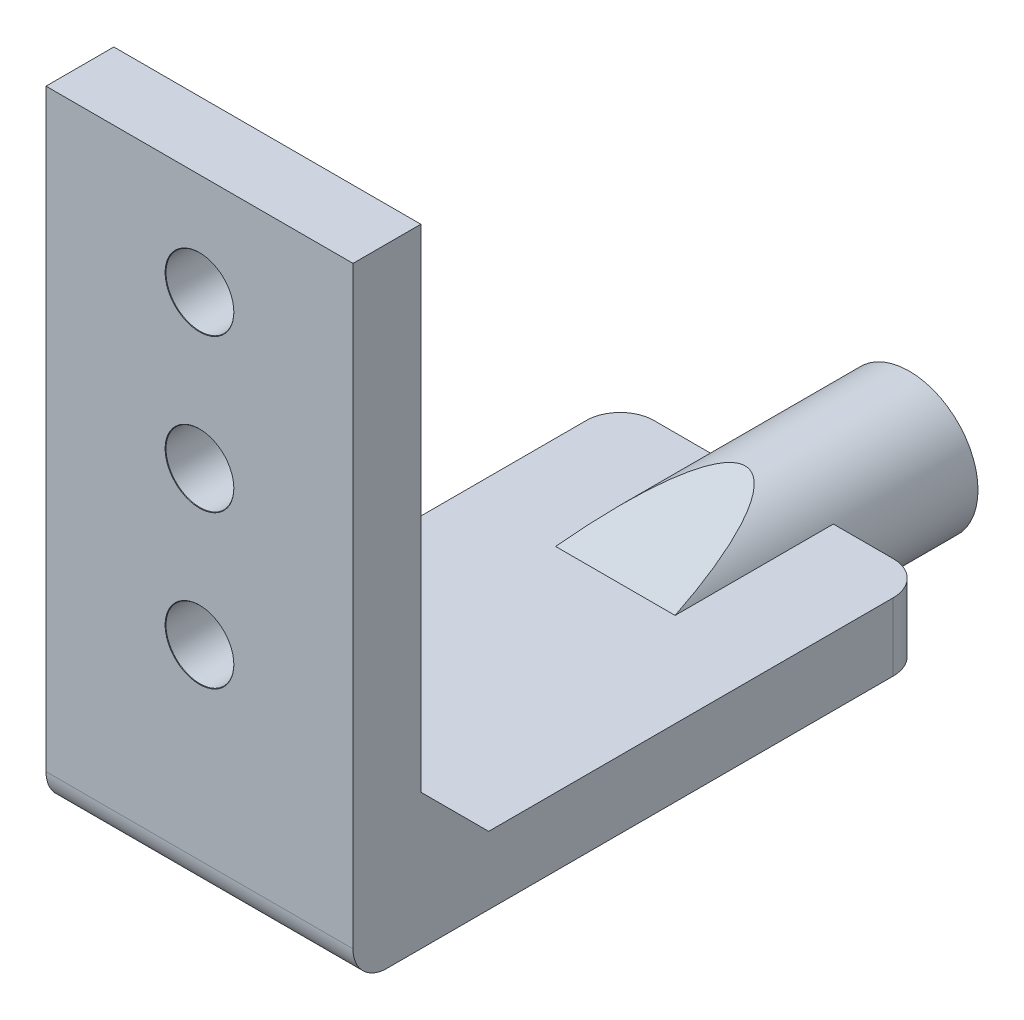
SolidWorks part; units mm, degrees
material "ABS"
ref_plane "Front Plane" through (0, 0, 0) normal (0, 0, 1) x (1, 0, 0)
ref_plane "Top Plane" through (0, 0, 0) normal (0, 1, 0) x (1, 0, 0)
ref_plane "Right Plane" through (0, 0, 0) normal (1, 0, 0) x (0, 0, -1)
sketch "Sketch1" plane through (0, 0, 0) normal (0, 0, 1) x (1, 0, 0)
  circle A0 centre (0, 0) radius 4.05
  dimension "D1" = 8.1
extrude "Boss-Extrude1" add sketch "Sketch1" along normal blind 8
sketch "Sketch2" plane through (0, 0, 8) normal (0, 0, 1) x (1, 0, 0)
  line L1 (-9.05, -2) -> (9.05, -2)
  line L2 (-9.05, -2) -> (-9.05, 2)
  line L3 (-9.05, 2) -> (9.05, 2)
  line L4 (9.05, -2) -> (9.05, 2)
  line L5 (-9.05, -2) -> (9.05, 2) construction
  line L6 (-9.05, 2) -> (9.05, -2) construction
  point P0 (0, 0)
  dimension "D1" = 4
  dimension "D2" = 18.1
extrude "Boss-Extrude2" add sketch "Sketch2" along normal blind 33.85
chamfer "Chamfer1" distance 2.5 angle 75 1 edges at (0, 2, 8) first distance on face at (0, 3.025, 8)
chamfer "Chamfer2" distance 2.5 angle 75 1 edges at (0, -2, 8) first distance on face at (0, -3.025, 8)
fillet "Fillet1" radius 2 2 edges at (-9.05, 0, 8) (9.05, 0, 8)
sketch "Sketch3" plane through (0, 2, 0) normal (0, 1, 0) x (1, 0, 0)
  line L0 (9.05, -41.85) -> (9.05, -10) construction
  line L1 (-9.05, -41.85) -> (9.05, -41.85)
  line L2 (-9.05, -41.85) -> (-9.05, -37.85)
  line L3 (-9.05, -37.85) -> (9.05, -37.85)
  line L4 (9.05, -41.85) -> (9.05, -37.85)
  dimension "D1" = 4
extrude "Boss-Extrude3" add sketch "Sketch3" along normal blind 33
chamfer "Chamfer3" distance 4 angle 45 1 edges at (0, 2, 37.85)
hole_wizard "Ø4.0mm Dowel Hole1" positions "Sketch4" profile "Sketch5" hole size "Ø4.0" standard "ANSI Metric" end condition through all
sketch "Sketch4" plane through (0, 0, 41.85) normal (0, 0, 1) x (1, 0, 0)
  line L0 (-9.05, 35) -> (9.05, 35) construction
  point P0 (0, 29)
  point P2 (0, 20)
  point P4 (0, 11)
  point P6 (0, 0)
  point P7 (0, 0)
  point P8 (0, 0)
  point P9 (0, 0)
  dimension "D1" = 6
  dimension "D2" = 9
  dimension "D3" = 9
sketch "Sketch5" plane through (0, 29, 41.85) normal (1, 0, 0) x (0, -1, 0)
  line L0 (0, 0) -> (0, 41.85)
  line L1 (0, 41.85) -> (2, 41.85)
  line L2 (2, 41.85) -> (2, 0.025)
  line L3 (2, 0.025) -> (2.025, 0)
  line L5 (2.025, 0) -> (0, 0)
  line L6 (-2, 0.025) -> (-2.025, 0) construction
  line L11 (0, -6.35) -> (0, 107.95) construction
  dimension "Thru Hole Dia." = 4
  dimension "Thru Hole Depth" = 41.85
  dimension "Near C'Sink Dia." = 4.05
  dimension "Near C'Sink Angle" = 90
fillet "Fillet2" radius 2 1 edges at (0, -2, 41.85)
